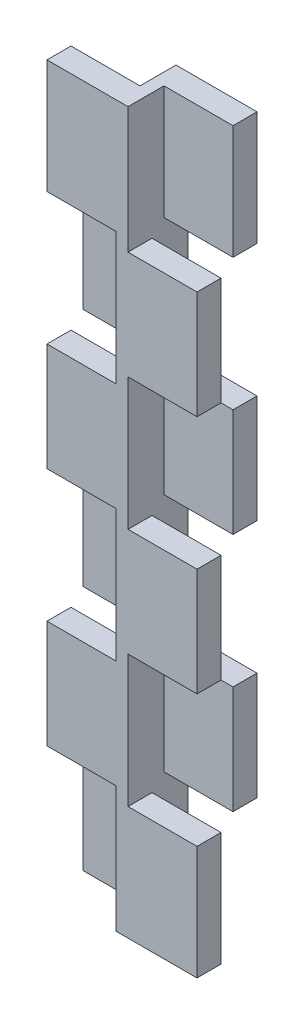
SolidWorks part; units mm, degrees
ref_plane "Front Plane" through (0, 0, 0) normal (0, 0, 1) x (1, 0, 0)
ref_plane "Top Plane" through (0, 0, 0) normal (0, 1, 0) x (1, 0, 0)
ref_plane "Right Plane" through (0, 0, 0) normal (1, 0, 0) x (0, 0, -1)
sketch "Sketch1" plane through (0, 0, 0) normal (0, 0, 1) x (1, 0, 0)
  line L1 (0, 0) -> (0.25, 0)
  line L2 (0, 0) -> (0, 1.2)
  line L3 (0, 1.2) -> (0.25, 1.2)
  line L4 (0.25, 0) -> (0.25, 1.2)
  dimension "D1" = 0.25
  dimension "D2" = 1.2
extrude "Boss-Extrude1" add sketch "Sketch1" along normal blind 0.1 contours L2 L3 L4 L1
sketch "Sketch2" plane through (0.25, 0, 0) normal (1, 0, 0) x (0, 0, -1)
  line L0 (-0.05, 1.2) -> (-0.05, 0) construction
  line L1 (-0.1, 1.2) -> (0, 1.2) construction
  line L2 (-0.1, 0) -> (0, 0) construction
  line L3 (-0.06, 1.2) -> (-0.06, 0) construction
  line L4 (-0.04, 0) -> (-0.04, 1.2) construction
  line L5 (-0.1, 0.6) -> (0, 0.6) construction
  line L6 (-0.1, 0) -> (-0.1, 1.2) construction
  line L7 (0, 0) -> (0, 1.2) construction
  line L8 (-0.1, 0.61) -> (0, 0.61) construction
  line L9 (-0.1, 0.59) -> (0, 0.59) construction
  line L10 (-0.1, 0.4) -> (0, 0.4) construction
  line L11 (-0.1, 0.41) -> (0, 0.41) construction
  line L12 (-0.1, 0.39) -> (0, 0.39) construction
  line L13 (-0.1, 0.8) -> (0, 0.8) construction
  line L14 (-0.1, 0.81) -> (0, 0.81) construction
  line L15 (-0.1, 1) -> (0, 1) construction
  line L16 (0, 1.01) -> (-0.1, 1.01) construction
  line L17 (-0.1, 0.99) -> (0, 0.99) construction
  line L18 (0, 0.79) -> (-0.1, 0.79) construction
  line L19 (-0.1, 0.2) -> (0, 0.2) construction
  line L20 (0, 0.21) -> (-0.1, 0.21) construction
  line L21 (0, 0.19) -> (-0.1, 0.19) construction
  line L22 (-0.04, 1.2) -> (-0.1, 1.2)
  line L23 (-0.1, 1.2) -> (-0.1, 0.99)
  line L24 (-0.1, 0.99) -> (-0.06, 0.99)
  line L25 (-0.06, 0.99) -> (-0.06, 0.81)
  line L26 (-0.06, 0.81) -> (-0.1, 0.81)
  line L27 (-0.1, 0.81) -> (-0.1, 0.59)
  line L28 (-0.1, 0.59) -> (-0.06, 0.59)
  line L29 (-0.06, 0.59) -> (-0.06, 0.41)
  line L30 (-0.06, 0.41) -> (-0.1, 0.41)
  line L31 (-0.1, 0.41) -> (-0.1, 0.19)
  line L32 (-0.1, 0.19) -> (-0.06, 0.19)
  line L33 (-0.06, 0.19) -> (-0.06, 0)
  line L34 (-0.06, 0) -> (0, 0)
  line L35 (0, 0) -> (0, 0.21)
  line L36 (0, 0.21) -> (-0.04, 0.21)
  line L37 (-0.04, 0.21) -> (-0.04, 0.39)
  line L38 (-0.04, 0.39) -> (0, 0.39)
  line L39 (0, 0.39) -> (0, 0.61)
  line L40 (0, 0.61) -> (-0.04, 0.61)
  line L41 (-0.04, 0.61) -> (-0.04, 0.79)
  line L42 (-0.04, 0.79) -> (0, 0.79)
  line L43 (0, 0.79) -> (0, 1.01)
  line L44 (0, 1.01) -> (-0.04, 1.01)
  line L45 (-0.04, 1.01) -> (-0.04, 1.2)
  dimension "D1" = 0.01
  dimension "D2" = 0.01
  dimension "D3" = 0.01
  dimension "D4" = 0.01
  dimension "D5" = 0.01
  dimension "D6" = 0.01
  dimension "D7" = 0.01
  dimension "D8" = 0.01
  dimension "D9" = 0.01
  dimension "D10" = 0.01
  dimension "D11" = 0.01
  dimension "D12" = 0.01
  dimension "D13" = 0.2
  dimension "D14" = 0.2
  dimension "D15" = 0.2
  dimension "D16" = 0.2
extrude "Cut-Extrude1" cut sketch "Sketch2" against normal blind 0.115
sketch "Sketch3" plane through (0, 0, 0) normal (-1, 0, 0) x (0, 0, 1)
  line L0 (0.05, 1.2) -> (0.05, 0) construction
  line L1 (0.1, 1.2) -> (0, 1.2) construction
  line L2 (0.1, 0) -> (0, 0) construction
  line L3 (0.06, 1.2) -> (0.06, 0) construction
  line L4 (0.04, 1.2) -> (0.04, 0) construction
  line L5 (0, 0.6) -> (0.1, 0.6) construction
  line L6 (0, 0) -> (0, 1.2) construction
  line L7 (0.1, 0) -> (0.1, 1.2) construction
  line L8 (0, 0.61) -> (0.1, 0.61) construction
  line L9 (0, 0.59) -> (0.1, 0.59) construction
  line L10 (0, 0.79) -> (0.1, 0.79) construction
  line L11 (0, 0.8) -> (0.1, 0.8) construction
  line L12 (0, 0.81) -> (0.1, 0.81) construction
  line L13 (0, 1.01) -> (0.1, 1.01) construction
  line L14 (0, 1) -> (0.1, 1) construction
  line L15 (0, 0.99) -> (0.1, 0.99) construction
  line L16 (0, 0.4) -> (0.1, 0.4) construction
  line L17 (0, 0.41) -> (0.1, 0.41) construction
  line L18 (0, 0.39) -> (0.1, 0.39) construction
  line L19 (0, 0.2) -> (0.1, 0.2) construction
  line L20 (0, 0.21) -> (0.1, 0.21) construction
  line L21 (0, 0.19) -> (0.1, 0.19) construction
  line L22 (0.06, 1.01) -> (0.06, 1.2)
  line L23 (0.06, 1.2) -> (0, 1.2)
  line L24 (0, 1.2) -> (0, 0.99)
  line L25 (0, 0.99) -> (0.04, 0.99)
  line L26 (0.04, 0.99) -> (0.04, 0.81)
  line L27 (0.04, 0.81) -> (0, 0.81)
  line L28 (0, 0.81) -> (0, 0.59)
  line L29 (0, 0.59) -> (0.04, 0.59)
  line L30 (0.04, 0.59) -> (0.04, 0.41)
  line L31 (0.04, 0.41) -> (0, 0.41)
  line L32 (0, 0.41) -> (0, 0.19)
  line L33 (0, 0.19) -> (0.04, 0.19)
  line L34 (0.04, 0.19) -> (0.04, 0)
  line L35 (0.04, 0) -> (0.1, 0)
  line L36 (0.1, 0) -> (0.1, 0.21)
  line L37 (0.1, 0.21) -> (0.06, 0.21)
  line L38 (0.06, 0.21) -> (0.06, 0.39)
  line L39 (0.06, 0.39) -> (0.1, 0.39)
  line L40 (0.1, 0.39) -> (0.1, 0.61)
  line L41 (0.1, 0.61) -> (0.06, 0.61)
  line L42 (0.06, 0.61) -> (0.06, 0.79)
  line L43 (0.06, 0.79) -> (0.1, 0.79)
  line L44 (0.1, 0.79) -> (0.1, 1.01)
  line L45 (0.1, 1.01) -> (0.06, 1.01)
  dimension "D1" = 0.01
  dimension "D2" = 0.01
  dimension "D3" = 0.01
  dimension "D4" = 0.01
  dimension "D5" = 0.01
  dimension "D6" = 0.01
  dimension "D8" = 0.01
  dimension "D9" = 0.01
  dimension "D11" = 0.01
  dimension "D12" = 0.01
  dimension "D13" = 0.2
  dimension "D16" = 0.2
  dimension "D7" = 0.2
  dimension "D10" = 0.2
  dimension "D14" = 0.01
  dimension "D15" = 0.01
extrude "Cut-Extrude2" cut sketch "Sketch3" against normal blind 0.115
equation "\"t\"= 0.25'thickness of the sheets"
equation "\"t_cf\"= 0.115'thickness of single carbon fiber layer"
equation "\"t_kapton\"= 0.025'thickness of single Kapton flex layer"
equation "\"t_fr4\"= 0.1'thickness of FR4 with copper layer"
equation "\"joint_flex\"= 0.1'Width of flextures gap"
equation "\"joint_flex_eff\"= 0.02'Width of flecture after castelation"
equation "\"joint_fold\"= 0.2'Width of folding joints for 90deg fold"
equation "\"gap_tolerance\"= 0.002'Width to have interfecence fit between carbon fiber inserts"
equation "\"assemble_angle\"= 90'Angle of assembly parts"
equation "\"link_lift\"= 0.5'Actuation linkage amplification for the lift motion"
equation "\"link_swing\"= 0.45'Actuation linkage amplification for the swing motion"
equation "\"D1@Sketch1\"=\"t\""
equation "\"D1@Boss-Extrude1\"=\"joint_flex\""
equation "\"D1@Sketch2\"=\"joint_flex_eff\"/2"
equation "\"D2@Sketch2\"=\"joint_flex_eff\"/2"
equation "\"fold_gap\"= 0.01"
equation "\"D3@Sketch2\"=\"fold_gap\""
equation "\"D4@Sketch2\"=\"fold_gap\""
equation "\"D5@Sketch2\"=\"fold_gap\""
equation "\"D6@Sketch2\"=\"fold_gap\""
equation "\"D7@Sketch2\"=\"fold_gap\""
equation "\"D8@Sketch2\"=\"fold_gap\""
equation "\"D9@Sketch2\"=\"fold_gap\""
equation "\"D10@Sketch2\"=\"fold_gap\""
equation "\"D11@Sketch2\"=\"fold_gap\""
equation "\"D12@Sketch2\"=\"fold_gap\""
equation "\"D1@Cut-Extrude1\"=\"t_cf\""
equation "\"D1@Sketch3\"=\"joint_flex_eff\"/2"
equation "\"D2@Sketch3\"=\"joint_flex_eff\"/2"
equation "\"D3@Sketch3\"=\"fold_gap\""
equation "\"D4@Sketch3\"=\"fold_gap\""
equation "\"D5@Sketch3\"=\"fold_gap\""
equation "\"D6@Sketch3\"=\"fold_gap\""
equation "\"D8@Sketch3\"=\"fold_gap\""
equation "\"D9@Sketch3\"=\"fold_gap\""
equation "\"D11@Sketch3\"=\"fold_gap\""
equation "\"D12@Sketch3\"=\"fold_gap\""
equation "\"D14@Sketch3\"=\"fold_gap\""
equation "\"D15@Sketch3\"=\"fold_gap\""
equation "\"D1@Cut-Extrude2\"=\"t_cf\""
